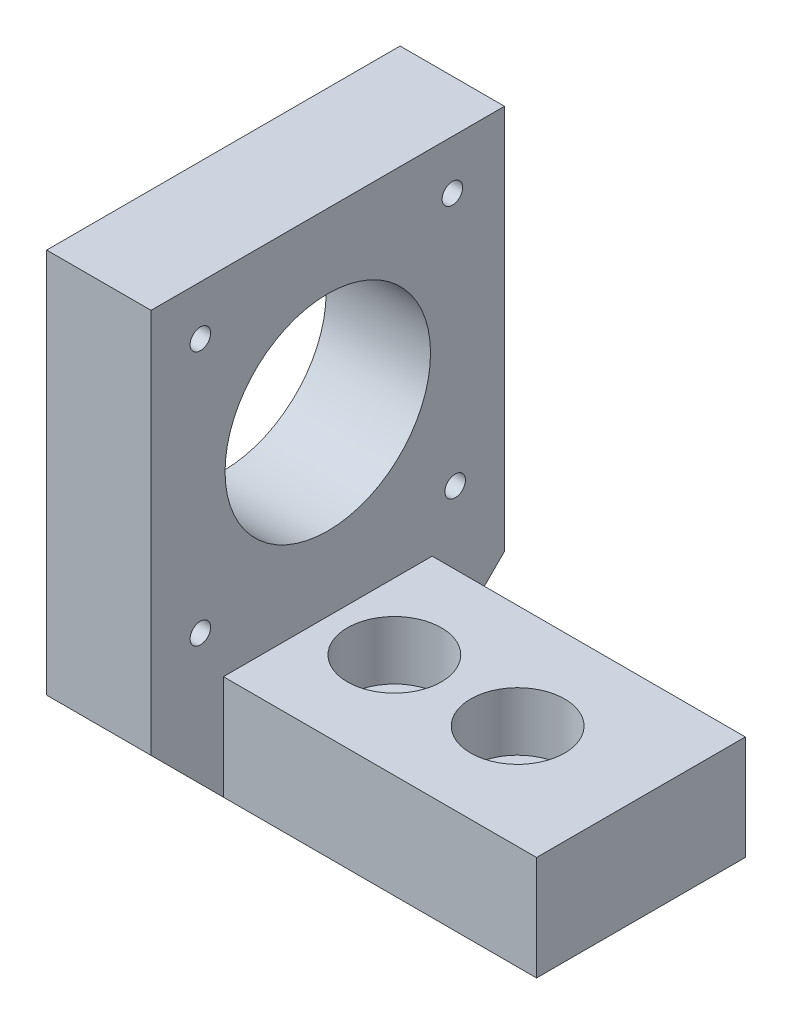
SolidWorks part; units mm, degrees
ref_plane "Front Plane" through (0, 0, 0) normal (0, 0, 1) x (1, 0, 0)
ref_plane "Top Plane" through (0, 0, 0) normal (0, 1, 0) x (1, 0, 0)
ref_plane "Right Plane" through (0, 0, 0) normal (1, 0, 0) x (0, 0, -1)
sketch "Sketch1" plane through (0, 0, 0) normal (0, 1, 0) x (1, 0, 0)
  line L1 (-25.4, -12.7) -> (25.4, -12.7)
  line L2 (-25.4, -12.7) -> (-25.4, 12.7)
  line L3 (-25.4, 12.7) -> (25.4, 12.7)
  line L4 (25.4, -12.7) -> (25.4, 12.7)
  line L5 (-25.4, -12.7) -> (25.4, 12.7) construction
  line L6 (-25.4, 12.7) -> (25.4, -12.7) construction
  point P0 (0, 0)
  dimension "D1" = 25.4
  dimension "D2" = 50.8
extrude "Boss-Extrude1" add sketch "Sketch1" along normal blind 12.7
sketch "Sketch2" plane through (-25.4, 0, 0) normal (-1, 0, 0) x (0, 0, 1)
  line L1 (-15.5, 18.7) -> (15.5, 18.7) construction
  line L2 (-15.5, 18.7) -> (-15.5, 49.7) construction
  line L3 (-15.5, 49.7) -> (15.5, 49.7) construction
  line L4 (15.5, 18.7) -> (15.5, 49.7) construction
  line L5 (-15.5, 18.7) -> (15.5, 49.7) construction
  line L6 (-15.5, 49.7) -> (15.5, 18.7) construction
  line L7 (-12.7, 12.7) -> (12.7, 12.7) construction
  line L8 (-21.5, 12.7) -> (21.5, 12.7)
  line L9 (-21.5, 12.7) -> (-21.5, 55.7)
  line L10 (-21.5, 55.7) -> (21.5, 55.7)
  line L11 (21.5, 12.7) -> (21.5, 55.7)
  line L12 (-21.5, 12.7) -> (21.5, 55.7) construction
  line L13 (-21.5, 55.7) -> (21.5, 12.7) construction
  circle A0 centre (0, 34.2) radius 12.5
  point P0 (0, 34.2)
  point P5 (0, 34.2)
  dimension "D3" = 25
  dimension "D1" = 31
  dimension "D2" = 43
extrude "Boss-Extrude2" add sketch "Sketch2" against normal blind 12.7
chamfer "Chamfer1" distance 12.7 angle 45 2 edges at (-19.05, 12.7, 12.7) (-19.05, 12.7, -12.7)
hole_wizard "Tap Drill for M3x0.5 Tap1" positions "Sketch3" profile "Sketch4" hole size "M3x0.5" standard "ANSI Metric" end condition through all
sketch "Sketch3" plane through (-25.4, 0, 0) normal (-1, 0, 0) x (0, 0, 1)
  line L0 (-15.5, 49.7) -> (15.5, 49.7) construction
  point P0 (-15.1608, 49.7)
  point P4 (15.5, 49.7)
  point P7 (15.5, 18.7)
  point P10 (-15.5, 18.7)
sketch "Sketch4" plane through (-25.4, 49.7, -15.1608) normal (0, 1, 0) x (0, 0, 1)
  line L0 (0, 0) -> (0, 50.8)
  line L1 (0, 50.8) -> (1.25, 50.8)
  line L2 (1.25, 50.8) -> (1.25, 0)
  line L5 (1.25, 0) -> (0, 0)
  line L11 (0, -6.35) -> (0, 107.95) construction
  dimension "Thru Hole Dia." = 2.5
  dimension "Thru Hole Depth" = 50.8
sketch "Sketch5" plane through (0, 12.7, 0) normal (0, 1, 0) x (1, 0, 0)
  line L0 (25.4, 0) -> (-12.7, 0) construction
  line L1 (25.4, -12.7) -> (25.4, 12.7) construction
  line L2 (-12.7, -21.5) -> (-12.7, 21.5) construction
  point P6 (10.4, 0)
  point P7 (-4.6, 0)
  dimension "D1" = 15
  dimension "D2" = 15
hole_wizard "1/4 Clearance Hole1" positions "Sketch6" profile "Sketch7" hole size "1/4" standard "ANSI Inch" end condition through all
sketch "Sketch6" plane through (0, 12.7, 0) normal (0, 1, 0) x (1, 0, 0)
  point P0 (-4.6, 0)
  point P3 (10.4, 0)
sketch "Sketch7" plane through (-4.6, 12.7, 0) normal (1, 0, 0) x (0, 0, 1)
  line L0 (0, 0) -> (0, 12.7)
  line L1 (0, 12.7) -> (3.3782, 12.7)
  line L2 (3.3782, 12.7) -> (3.3782, 0)
  line L5 (3.3782, 0) -> (0, 0)
  line L11 (0, -6.35) -> (0, 107.95) construction
  dimension "Thru Hole Dia." = 6.7564
  dimension "Thru Hole Depth" = 12.7
sketch "Sketch8" plane through (0, 12.7, 0) normal (0, 1, 0) x (1, 0, 0)
  circle A0 centre (-4.6, 0) radius 5.715
  circle A1 centre (10.4, 0) radius 5.715
  dimension "D1" = 11.43
extrude "Cut-Extrude1" cut sketch "Sketch8" against normal blind 7.112
